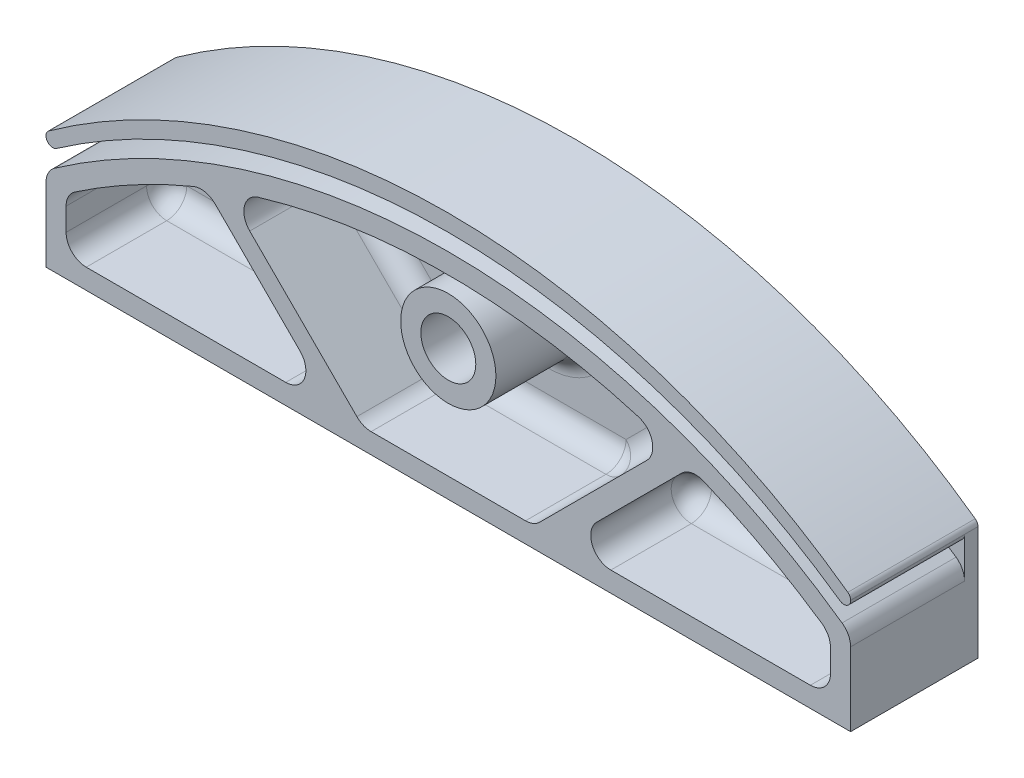
SolidWorks part; units mm, degrees
ref_plane "Front Plane" through (0, 0, 0) normal (0, 0, 1) x (1, 0, 0)
ref_plane "Top Plane" through (0, 0, 0) normal (0, 1, 0) x (1, 0, 0)
ref_plane "Right Plane" through (0, 0, 0) normal (1, 0, 0) x (0, 0, -1)
sketch "Sketch1" plane through (0, 0, 0) normal (0, 0, 1) x (1, 0, 0)
  line L2 (-2.4718, 1.7) -> (2.4718, 1.7)
  line L3 (-4.0792, 5.75) -> (4.0792, 5.75)
  arc A0 (-2.4718, 1.7) -> (2.4718, 1.7) centre (0, 0) ccw
  arc A2 (-4.0792, 5.75) -> (4.0792, 5.75) centre (0, 0) ccw
  arc A4 (-4.0792, 5.75) -> (4.0792, 5.75) centre (0, 0) cw
  arc A5 (-2.4718, 1.7) -> (2.4718, 1.7) centre (0, 0) cw
  arc A6 (-2.5542, 1.7567) -> (2.5542, 1.7567) centre (0, 0) cw
  arc A7 (-2.5542, 1.7567) -> (2.5542, 1.7567) centre (0, 0) ccw
  dimension "D1" = 6
  dimension "D2" = 1.7
  dimension "D3" = 0.1
extrude "Boss-Extrude1" add sketch "Sketch1" along normal blind 15 contours A4 L3 | L3 A2 A7 A6 region at (0, 6.2743, 0) region at (0, 5.5596, 0)
sketch "Sketch2" plane through (0, 0, 0) normal (0, 0, 1) x (1, 0, 0)
  line L0 (0, 7.05) -> (0, -7.05) construction
  line L5 (-60, 0) -> (60, 0) construction
  line L6 (0, 0) -> (0, -19.5) construction
  line L7 (0, -19.5) -> (-60, -19.5)
  line L8 (0, -19.5) -> (60, -19.5)
  line L9 (-60, -19.5) -> (-60, -7)
  line L10 (-60, -7) -> (-12.5, -7)
  line L11 (-12.5, 0) -> (-12.5, -7)
  line L12 (12.5, 0) -> (12.5, -7)
  line L13 (60, -19.5) -> (60, -7)
  line L14 (60, -7) -> (12.5, -7)
  arc A0 (60, -7) -> (0, 12.5) centre (0, -89.5577) ccw
  circle A1 centre (0, 0) radius 12.5
  arc A2 (0, 12.5) -> (-60, -7) centre (0, -89.5577) ccw
  point P9 (0, 0)
  dimension "D1" = 25
  dimension "D2" = 19.5
  dimension "D3" = 12.5
extrude "Boss-Extrude2" add sketch "Sketch2" along normal blind 17 from surface contours A1 L11 L10 L9 L7 L8 L13 L14 L12 | A1 | A1 A2 L10 L11 | A1 L12 L14 A0 region at (0, -13.4205, 0) region at (-28.9581, 0.5905, 0) region at (28.9581, 0.5905, 0) region at (0, 0, 0) starting at face at (7.05, 0, 0)
sketch "Sketch5" plane through (0, 0, 0) normal (0, 0, -1) x (-1, 0, 0)
  circle A0 centre (0, 0) radius 4.1
  dimension "D1" = 8.2
extrude "Cut-Extrude1" cut sketch "Sketch5" against normal blind 24
sketch "Sketch6" plane through (0, 0, 0) normal (0, 0, -1) x (-1, 0, 0)
  line L1 (60, -19.5) -> (-60, -19.5)
  line L2 (60, -19.5) -> (60, -4.5)
  line L3 (60, -4.5) -> (-60, -4.5)
  line L4 (-60, -19.5) -> (-60, -4.5)
  line L5 (0, 12.5) -> (0, 15)
  line L6 (-60, -4.5) -> (-60, -2)
  line L7 (60, -4.5) -> (60, -2)
  line L8 (0, 15) -> (0, 17.5)
  arc A0 (-60, -4.5) -> (60, -4.5) centre (0, -87.0577) cw
  arc A1 (60, -7) -> (-60, -7) centre (0, -89.5577) ccw construction
  arc A2 (-60, -2) -> (60, -2) centre (0, -84.5577) cw
  circle M8 centre (0, 0) radius 4.1
  line M9 (-60, -7) -> (-60, -19.5)
  line M10 (-60, -19.5) -> (60, -19.5)
  line M11 (60, -19.5) -> (60, -7)
  arc M12 (60, -7) -> (-60, -7) centre (0, -89.5577) ccw
  dimension "D1" = 15
  dimension "D2" = 2.5
  dimension "D3" = 2.5
  dimension "D4" = 2.5
extrude "Boss-Extrude3" add sketch "Sketch6" along normal blind 2 contours L3 M12 M9 M10 M11 | L3 M12 M8 | A0 L3 L5 M12 | A2 L6 A0 L8 | A0 L5 L3 M12 | A2 L8 A0 L7 | L4 L3 M12 | L2 L3 M12 region at (0, -12.033, 0) region at (-58.8092, -5.327, 0) region at (58.8092, -5.327, 0) region at (-31.7421, 10.6104, 0) region at (-58.2, -3.8691, 0) region at (0, -4.3859, 0) region at (31.3496, 9.4027, 0) region at (59.3609, -3.25, 0)
extrude "Boss-Extrude4" add sketch "Sketch6<3>" against normal blind 17 contours A2 L6 A0 L8 | A2 L8 A0 L7 region at (-31.7421, 10.6104, 0) region at (59.3609, -3.25, 0)
sketch "Sketch6<3>" plane through (0, 0, 0) normal (0, 0, -1) x (-1, 0, 0) same geometry as "Sketch6"
sketch "Sketch7" plane through (0, 0, 17) normal (0, 0, 1) x (1, 0, 0)
  line L0 (17, -16.5) -> (57, -16.5)
  line L3 (-36.163, 2.663) -> (-17, -16.5)
  line L4 (-12.7574, -16.5) -> (-33.0731, 3.8157)
  line L5 (0, 0) -> (0, -9.8778) construction
  line L6 (57, -16.5) -> (57, -8.5427)
  line L7 (-57, -8.5427) -> (-57, -16.5)
  line L8 (-57, -16.5) -> (57, -16.5)
  line L9 (57, -16.5) -> (57, -8.5427)
  line L10 (-57, -8.5427) -> (-57, -16.5)
  line L11 (-57, -16.5) -> (-17, -16.5)
  line L12 (12.7574, -16.5) -> (33.0731, 3.8157)
  line L13 (36.163, 2.663) -> (17, -16.5)
  line L14 (-12.7574, -16.5) -> (12.7574, -16.5)
  arc A0 (33.0731, 3.8157) -> (-33.0731, 3.8157) centre (0, -89.5577) ccw
  arc A2 (57, -8.5427) -> (-57, -8.5427) centre (0, -89.5577) ccw
  arc A3 (57, -8.5427) -> (36.163, 2.663) centre (0, -89.5577) ccw
  arc A4 (-36.163, 2.663) -> (-57, -8.5427) centre (0, -89.5577) ccw
  circle A5 centre (0, 0) radius 7.1
  circle A6 centre (0, 0) radius 7.1
  point P9 (-19.1735, -16.5)
  point P15 (-18.6214, -16.5)
  dimension "D3" = 45
  dimension "D4" = 3
  dimension "D5" = 40
  dimension "D1" = 3
  dimension "D2" = 3
extrude "Cut-Extrude2" cut sketch "Sketch7" against normal blind 15
fillet "Fillet1" radius 3 27 edges at (37, -16.5, 2) (26.5815, -6.9185, 2) (46.9173, -2.3155, 2) (57, -12.5214, 2) (-26.5815, -6.9185, 2) (-37, -16.5, 2) (-57, -12.5214, 2) (-46.9173, -2.3155, 2) (-22.9152, -6.3421, 2) (0, 9.5, 2) (22.9152, -6.3421, 2) (0, -16.5, 2) (7.1, 0, 2) (-60, -7, 8.5) (60, -7, 8.5) (57, -16.5, 9.5) (57, -8.5427, 9.5) (36.163, 2.663, 9.5) (17, -16.5, 9.5) (33.0731, 3.8157, 9.5) (12.7574, -16.5, 9.5) (-33.0731, 3.8157, 9.5) (-12.7574, -16.5, 9.5) (-57, -8.5427, 9.5) (-57, -16.5, 9.5) (-17, -16.5, 9.5) (-36.163, 2.663, 9.5)
fillet "Fillet2" radius 1 4 edges at (60, -2, 7.5) (-60, -2, 7.5) (-60, -4.5, 8.5) (60, -4.5, 8.5)
